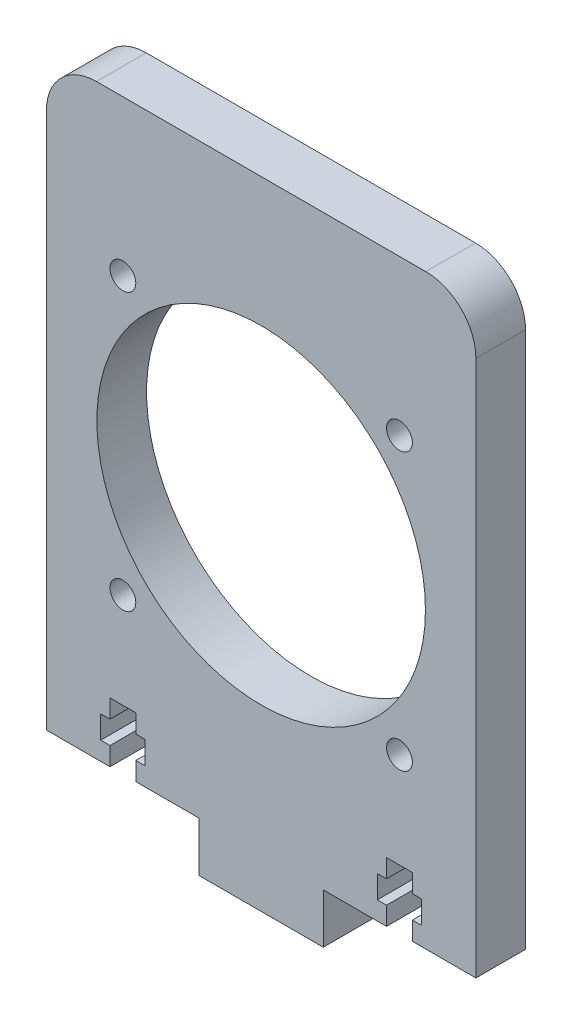
SolidWorks part; units mm, degrees
ref_plane "Front Plane" through (0, 0, 0) normal (0, 0, 1) x (1, 0, 0)
ref_plane "Top Plane" through (0, 0, 0) normal (0, 1, 0) x (1, 0, 0)
ref_plane "Right Plane" through (0, 0, 0) normal (1, 0, 0) x (0, 0, -1)
sketch "Sketch1" plane through (0, 0, 0) normal (0, 0, 1) x (1, 0, 0)
  line L0 (0, 0) -> (-35.3553, 35.3553) construction
  line L1 (-54.9, 75) -> (54.9, 75)
  line L2 (-54.9, 75) -> (-54.9, -75)
  line L3 (-54.9, -75) -> (54.9, -75)
  line L4 (54.9, 75) -> (54.9, -75)
  line L7 (-54.9, 0) -> (54.9, 0) construction
  line L8 (0, 75) -> (0, -75) construction
  circle A0 centre (0, 0) radius 42
  circle A1 centre (-35.3553, 35.3553) radius 3.3
  circle A2 centre (35.3553, 35.3553) radius 3.3
  circle A3 centre (35.3553, -35.3553) radius 3.3
  circle A4 centre (-35.3553, -35.3553) radius 3.3
  dimension "D1" = 84
  dimension "D5" = 6.6
  dimension "D2" = 109.8
  dimension "D3" = 150
  dimension "D4" = 45
  dimension "D6" = 50
extrude "Boss-Extrude1" add sketch "Sketch1" along normal blind 12.7 contours L4 L1 L2 L3 A2 A1 A0 A3 A4 region at (0, 73.1411, 0)
sketch "Sketch2" plane through (0, 0, 0) normal (0, 0, -1) x (-1, 0, 0)
  line L0 (0, -75) -> (32.05, -75)
  line L1 (54.9, -75) -> (-54.9, -75) construction
  line L2 (32.05, -75) -> (32.05, -70.3)
  line L3 (32.05, -70.3) -> (29.686, -70.3)
  line L4 (29.686, -70.3) -> (29.686, -64.46)
  line L5 (29.686, -64.46) -> (32.05, -64.46)
  line L6 (32.05, -64.46) -> (32.05, -59.76)
  line L7 (32.05, -59.76) -> (38.65, -59.76)
  line L8 (38.65, -59.76) -> (38.65, -64.46)
  line L9 (38.65, -64.46) -> (41.014, -64.46)
  line L10 (41.014, -64.46) -> (41.014, -70.3)
  line L11 (41.014, -70.3) -> (38.65, -70.3)
  line L12 (38.65, -70.3) -> (38.65, -75)
  line L13 (38.65, -75) -> (32.05, -75)
  line L14 (0, -75) -> (0, 0) construction
  line L15 (-38.65, -75) -> (-32.05, -75)
  line L16 (-38.65, -70.3) -> (-38.65, -75)
  line L17 (-41.014, -70.3) -> (-38.65, -70.3)
  line L18 (-41.014, -64.46) -> (-41.014, -70.3)
  line L19 (-38.65, -64.46) -> (-41.014, -64.46)
  line L20 (-38.65, -59.76) -> (-38.65, -64.46)
  line L21 (-32.05, -59.76) -> (-38.65, -59.76)
  line L22 (-32.05, -64.46) -> (-32.05, -59.76)
  line L23 (-29.686, -64.46) -> (-32.05, -64.46)
  line L24 (-29.686, -70.3) -> (-29.686, -64.46)
  line L25 (-32.05, -70.3) -> (-29.686, -70.3)
  line L26 (-32.05, -75) -> (-32.05, -70.3)
  line M18 (-54.9, -75) -> (54.9, -75)
  dimension "D1" = 32.05
  dimension "D2" = 5.84
  dimension "D3" = 6.6
  dimension "D4" = 15.24
  dimension "D5" = 11.328
extrude "Cut-Extrude1" cut sketch "Sketch2" against normal through all contours L26 L25 L24 L23 L22 L21 L20 L19 L18 L17 L16 M18 | L2 L3 L4 L5 L6 L7 L8 L9 L10 L11 L12 L13 region at (35.35, -67.38, 0)
sketch "Sketch4" plane through (0, -75, 0) normal (0, -1, 0) x (1, 0, 0)
  line L0 (0, 0) -> (15.875, 0)
  line L1 (-32.05, 0) -> (32.05, 0) construction
  line L2 (15.875, 0) -> (15.875, 12.7)
  line L3 (-32.05, 12.7) -> (32.05, 12.7) construction
  line L4 (15.875, 12.7) -> (-15.875, 12.7)
  line L7 (0, 0) -> (-15.875, 0)
  line L8 (-15.875, 0) -> (-15.875, 12.7)
  dimension "D1" = 31.75
extrude "Boss-Extrude2" add sketch "Sketch4" along normal blind 12.7
fillet "Fillet1" radius 12.8 2 edges at (-54.9, 75, 6.35) (54.9, 75, 6.35)
